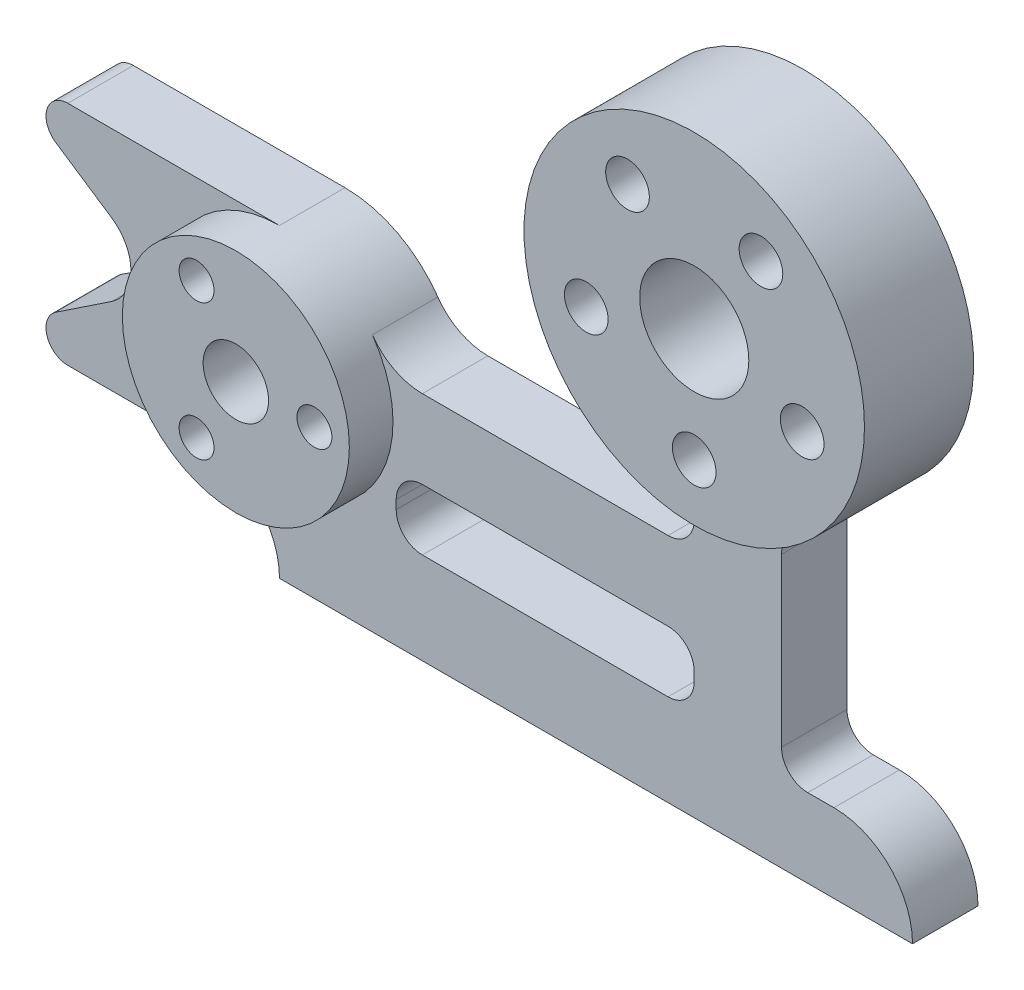
SolidWorks part; units mm, degrees
ref_plane "Спереди" through (0, 0, 0) normal (0, 0, 1) x (1, 0, 0)
ref_plane "Сверху" through (0, 0, 0) normal (0, 1, 0) x (1, 0, 0)
ref_plane "Справа" through (0, 0, 0) normal (1, 0, 0) x (0, 0, -1)
sketch "Эскиз1" plane through (0, 0, 0) normal (0, 0, 1) x (1, 0, 0)
  line L0 (-177.2736, 0) -> (470.1301, 0) construction
  line L1 (0, 26) -> (-65, 26) construction
  line L2 (-65, 26) -> (-26, 0) construction
  line L3 (-48.4861, 26) -> (0, 26)
  line L4 (-18, -26) -> (-65, -26) construction
  line L5 (-65, -26) -> (-26, 0) construction
  line L6 (-48.4861, -26) -> (-18, -26)
  line L7 (-51.2596, 16.8397) -> (-38.4808, 8.3205)
  line L8 (-51.2596, -16.8397) -> (-38.4808, -8.3205)
  line L9 (0, 0) -> (0, -44) construction
  line L10 (0, -44) -> (145, -44)
  line L11 (105, 139.9921) -> (105, -77.1477) construction
  line L12 (95, 18.2675) -> (95, 15)
  line L13 (115, 18.2675) -> (115, -20)
  line L14 (121, -26) -> (127, -26)
  line L15 (32.7261, -23) -> (89, -23)
  line L16 (32.7261, -9) -> (89, -9)
  line L17 (32.7261, 9) -> (89, 9)
  line L18 (95, -15) -> (95, -17)
  line L19 (60.8631, -9) -> (60.8631, -23) construction
  line L20 (26.7261, -15) -> (26.7261, -17)
  line L21 (60.8631, 9) -> (60.8631, -9) construction
  circle A0 centre (0, 0) radius 7.5
  circle A1 centre (0, 0) radius 26
  circle A2 centre (18, 0) radius 4
  circle A3 centre (-9, -15.5885) radius 4
  circle A4 centre (-9, 15.5885) radius 4
  arc A5 (-48.4861, 26) -> (-51.2596, 16.8397) centre (-48.4861, 21) ccw
  arc A6 (-48.4861, -26) -> (-51.2596, -16.8397) centre (-48.4861, -21) cw
  arc A7 (-38.4808, -8.3205) -> (-38.4808, 8.3205) centre (-44.0278, 0) ccw
  arc A8 (0, -44) -> (-18, -26) centre (-18, -44) ccw
  circle A9 centre (105, 63) radius 39
  circle A10 centre (105, 63) radius 12.5
  circle A11 centre (105, 37) radius 5
  circle A12 centre (80.2725, 54.9656) radius 5
  circle A13 centre (89.7176, 84.0344) radius 5
  circle A14 centre (120.2824, 84.0344) radius 5
  circle A15 centre (129.7275, 54.9656) radius 5
  arc A16 (7.74, 24.8212) -> (66.0632, 65.2197) centre (21.1362, 67.781) ccw
  arc A17 (145, -44) -> (127, -26) centre (127, -44) ccw
  arc A18 (115, -20) -> (121, -26) centre (121, -20) ccw
  arc A19 (120.9184, 27.3966) -> (115, 18.2675) centre (125, 18.2675) ccw
  arc A20 (95, 18.2675) -> (89.0816, 27.3966) centre (85, 18.2675) ccw
  arc A21 (89, -23) -> (95, -17) centre (89, -17) ccw
  arc A22 (95, -15) -> (89, -9) centre (89, -15) ccw
  arc A24 (89, 9) -> (95, 15) centre (89, 15) ccw
  arc A25 (21.272, 14.95) -> (32.7261, 9) centre (32.7261, 23) ccw
  arc A29 (26.7261, -15) -> (32.7261, -9) centre (32.7261, -15) cw
  arc A30 (32.7261, -23) -> (26.7261, -17) centre (32.7261, -17) cw
  point P15 (0, 0)
  point P49 (105, 63)
  dimension "D1" = 15
  dimension "D2" = 52
  dimension "D3" = 8
  dimension "D7" = 10
  dimension "D8" = 20
  dimension "D9" = 36
  dimension "D12" = 78
  dimension "D14" = 25
  dimension "D15" = 10
  dimension "D18" = 90
  dimension "D19" = 18
  dimension "D21" = 12
  dimension "D22" = 20
  dimension "D23" = 20
  dimension "D24" = 12
  dimension "D25" = 18
  dimension "D26" = 12
  dimension "D28" = 12
  dimension "D29" = 28
  dimension "D4" = 18
  dimension "D6" = 65
  dimension "D10" = 145
  dimension "D11" = 105
  dimension "D13" = 63
  dimension "D16" = 26
  dimension "D20" = 20
  dimension "D31" = 14
  dimension "D5" = 3
  dimension "D17" = 5
extrude "Бобышка-Вытянуть1" add sketch "Эскиз1" along normal blind 15 contours A25 A1 L16 A22 L18 A21 L15 L6 A8 L10 A17 L14 A18 L13 A19 A9 A20 L12 A24 L17 region at (-24.2431, 23.8906, 0)
extrude "Бобышка-Вытянуть4" add sketch "Эскиз1<3>" along normal blind 25 contours A9 A15 A14 A13 A12 A11 A10 | A1 A4 A3 A2 A0 region at (3.8039, 24.9766, 0) region at (106.0789, 100.8816, 0)
sketch "Эскиз1<3>" plane through (0, 0, 0) normal (0, 0, 1) x (1, 0, 0) same geometry as "Эскиз1"
extrude "Бобышка-Вытянуть5" add sketch "Эскиз1<4>" along normal blind 10 contours A7 L8 A6 L6 A1 L3 A5 L7 region at (-24.2431, 23.8906, 0)
sketch "Эскиз1<4>" plane through (0, 0, 0) normal (0, 0, 1) x (1, 0, 0) same geometry as "Эскиз1"
